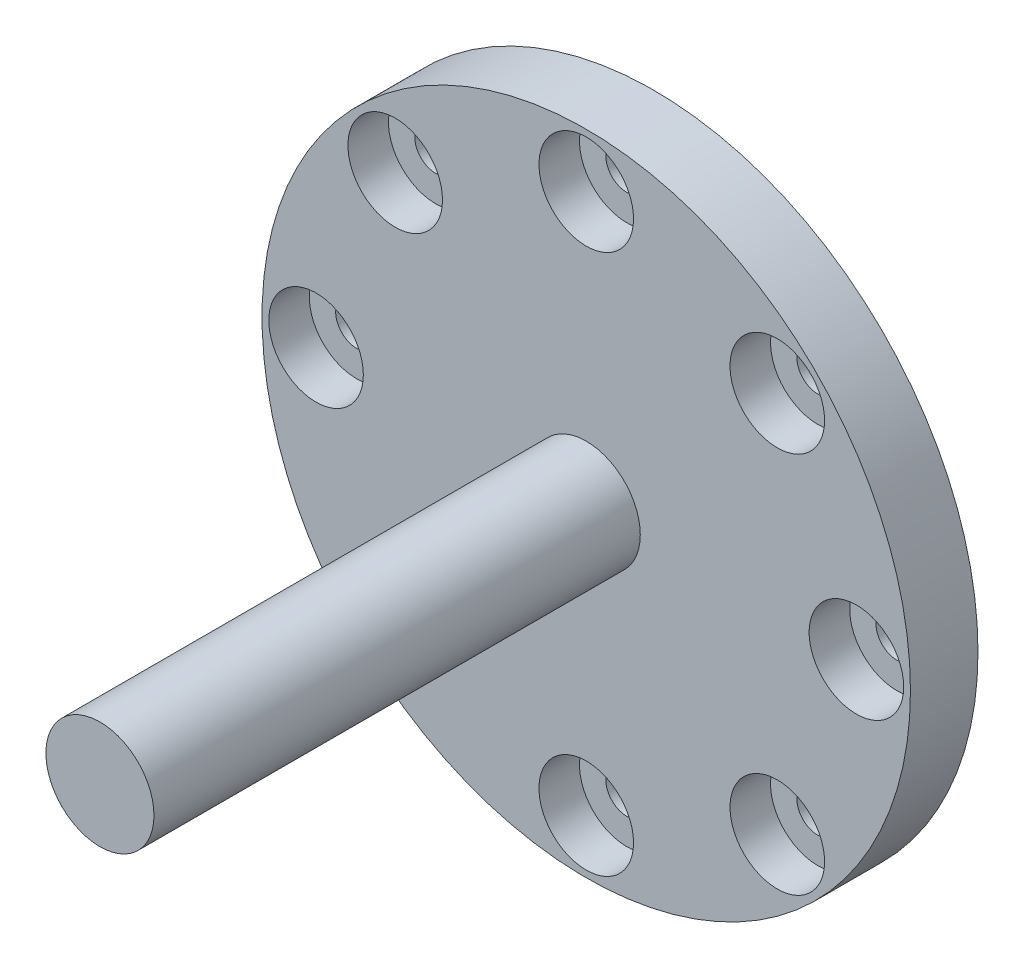
SolidWorks part; units mm, degrees
ref_plane "Front Plane" through (0, 0, 0) normal (0, 0, 1) x (1, 0, 0)
ref_plane "Top Plane" through (0, 0, 0) normal (0, 1, 0) x (1, 0, 0)
ref_plane "Right Plane" through (0, 0, 0) normal (1, 0, 0) x (0, 0, -1)
ref_axis "Axis1" through (0, 0, 5.5) along (0, 0, -1)
sketch "Sketch6" plane through (0, 0, 0) normal (0, 0, 1) x (1, 0, 0)
  circle A0 centre (0, 0) radius 24
extrude "Boss-Extrude1" add sketch "Sketch6" along normal blind 5
sketch "Sketch8" plane through (0, 0, 0) normal (0, 0, -1) x (-1, 0, 0)
  line L0 (0, 20) -> (0, 0) construction
  circle A0 centre (0, 20) radius 1.55
  circle A1 centre (14.1421, 14.1421) radius 1.55
  circle A2 centre (20, 0) radius 1.55
  circle A3 centre (14.1421, -14.1421) radius 1.55
  circle A4 centre (0, -20) radius 1.55
  circle A5 centre (-14.1421, -14.1421) radius 1.55
  circle A6 centre (-20, 0) radius 1.55
  circle A7 centre (-14.1421, 14.1421) radius 1.55
  dimension "D1" = 8
extrude "Cut-Extrude6" cut sketch "Sketch8" against normal up to surface (5 mm away) up to face at (24, 0, 5)
sketch "Sketch10" plane through (0, 0, 5) normal (0, 0, 1) x (1, 0, 0)
  circle A0 centre (0, 0) radius 4
extrude "Boss-Extrude2" add sketch "Sketch10" along normal blind 36
sketch "Sketch11" plane through (0, 0, 5) normal (0, 0, 1) x (1, 0, 0)
  circle A0 centre (0, 20) radius 3.5
  circle A1 centre (14.1421, 14.1421) radius 3.5
  circle A2 centre (20, 0) radius 3.5
  circle A3 centre (14.1421, -14.1421) radius 3.5
  circle A4 centre (0, -20) radius 3.5
  circle A5 centre (-14.1421, -14.1421) radius 3.5
  circle A6 centre (-20, 0) radius 3.5
  circle A7 centre (-14.1421, 14.1421) radius 3.5
  point P19 (0, 0)
  dimension "D1" = 8
extrude "Cut-Extrude8" cut sketch "Sketch11" against normal blind 3
ref_plane "Plane1" through (0, 0, 0) normal (1, 0, 0) x (0, 0, -1)
